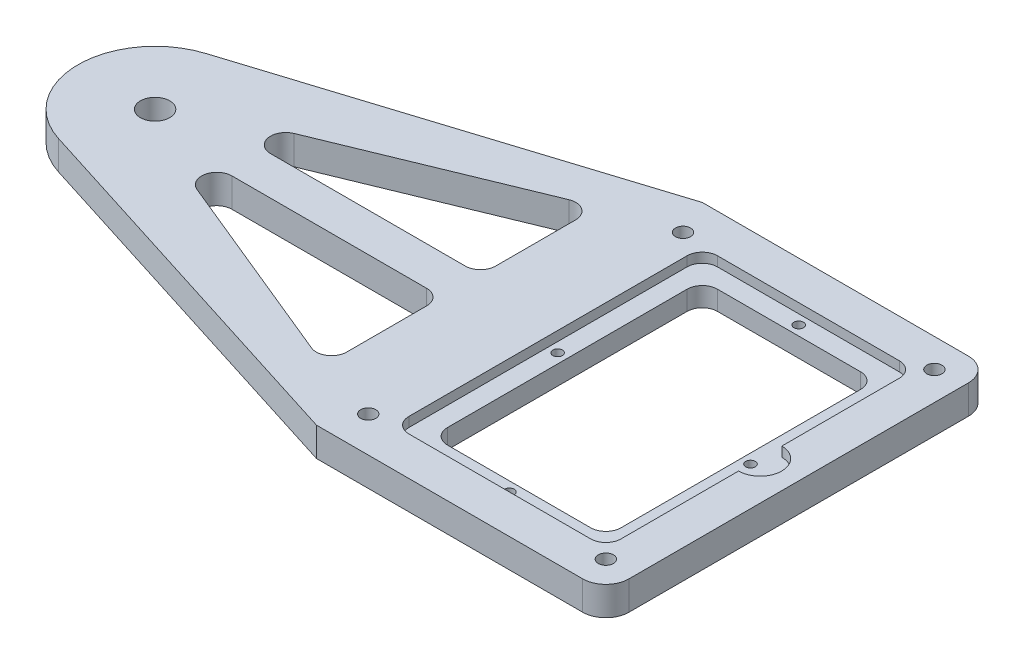
SolidWorks part; units mm, degrees
material "UHMW"
ref_plane "Front Plane" through (0, 0, 0) normal (0, 0, 1) x (1, 0, 0)
ref_plane "Top Plane" through (0, 0, 0) normal (0, 1, 0) x (1, 0, 0)
ref_plane "Right Plane" through (0, 0, 0) normal (1, 0, 0) x (0, 0, -1)
sketch "Sketch1" plane through (0, 0, 0) normal (0, 1, 0) x (1, 0, 0)
  line L0 (-47.625, 0) -> (47.625, 0) construction
  line L1 (-47.625, -63.5) -> (47.625, -63.5)
  line L2 (-47.625, -63.5) -> (-47.625, 63.5)
  line L3 (-47.625, 63.5) -> (47.625, 63.5)
  line L4 (47.625, -63.5) -> (47.625, 63.5)
  line L5 (-47.625, -63.5) -> (47.625, 63.5) construction
  line L6 (-47.625, 63.5) -> (47.625, -63.5) construction
  point P0 (0, 0)
  dimension "D1" = 95.25
  dimension "D2" = 127
  dimension "D3" = 63.5
extrude "Boss-Extrude1" add sketch "Sketch1" along normal blind 9.525
sketch "Sketch4" plane through (0, 9.525, 0) normal (0, 1, 0) x (1, 0, 0)
  line L1 (-47.625, 63.5) -> (-171.916, 24.2193)
  line L5 (-47.625, 63.5) -> (-47.625, -63.5) construction
  line L9 (-47.625, -63.5) -> (-171.916, -24.2193)
  line L10 (-47.625, 63.5) -> (-47.625, -63.5)
  arc A0 (-171.916, 24.2193) -> (-171.916, -24.2193) centre (-164.2618, 0) ccw
  circle A1 centre (-48.9458, 0) radius 2.5 construction
  dimension "D1" = 50.8
  dimension "D2" = 115.316
extrude "Boss-Extrude3" add sketch "Sketch4" against normal blind 9.525
sketch "Sketch5" plane through (0, 9.525, 0) normal (0, 1, 0) x (1, 0, 0)
  circle A0 centre (-164.2618, 0) radius 4.826
  circle A1 centre (-8.6868, 0) radius 4.826
  arc A2 (-171.916, 24.2193) -> (-171.916, -24.2193) centre (-164.2618, 0) ccw construction
  arc A3 (-171.916, 24.2193) -> (-171.916, -24.2193) centre (-164.2618, 0) ccw
  dimension "D1" = 9.652
  dimension "D2" = 155.575
extrude "Cut-Extrude1" cut sketch "Sketch5" against normal through all contours A0 | A1 region at (-164.2618, 9.525, 0) region at (-8.6868, 9.525, 0)
sketch "Sketch6" plane through (0, 9.525, 0) normal (0, 1, 0) x (1, 0, 0)
  line L0 (-63.5, 6.35) -> (-63.5, -6.35) construction
  line L1 (-63.5, 45.1637) -> (-157.9118, 6.35)
  line L2 (-157.9118, 6.35) -> (-63.5, 6.35)
  line L3 (-63.5, 6.35) -> (-63.5, 45.1637)
  line L4 (-63.5, -6.35) -> (-63.5, -45.1637)
  line L5 (-63.5, -45.1637) -> (-157.9118, -6.35)
  line L6 (-157.9118, -6.35) -> (-63.5, -6.35)
  line L7 (0, 0) -> (-63.5, 0) construction
  line L8 (-47.625, 63.5) -> (-171.916, 24.2193) construction
  line L9 (-189.6618, 78.2466) -> (-189.6618, -78.2466) construction
  arc A1 (-171.916, 24.2193) -> (-171.916, -24.2193) centre (-164.2618, 0) ccw construction
  point P10 (-189.6618, 0)
  dimension "D1" = 12.7
  dimension "D2" = 31.75
  dimension "D3" = 12.7
  dimension "D4" = 63.5
extrude "Cut-Extrude2" cut sketch "Sketch6" against normal through all
fillet "Fillet9" radius 5 6 edges at (-157.9118, 4.7625, 6.35) (-63.5, 4.7625, 6.35) (-63.5, 4.7625, 45.1637) (-63.5, 4.7625, -6.35) (-157.9118, 4.7625, -6.35) (-63.5, 4.7625, -45.1637)
sketch "Sketch7" plane through (0, 9.525, 0) normal (0, 1, 0) x (1, 0, 0)
  circle A0 centre (-8.6868, 0) radius 5.4538
extrude "Boss-Extrude4" add sketch "Sketch7" against normal blind 6.35
sketch "Sketch8" plane through (0, 9.525, 0) normal (0, 1, 0) x (1, 0, 0)
  line L4 (-47.625, -63.5) -> (47.625, -63.5) construction
  line L5 (-34.925, 50.8) -> (-34.925, -50.8)
  line L7 (-47.625, 63.5) -> (-47.625, -63.5) construction
  line L8 (-171.916, -24.2193) -> (-47.625, -63.5) construction
  line L10 (47.625, 50.8) -> (-47.625, 50.8)
  line L11 (34.925, 50.8) -> (-34.925, 50.8)
  line L13 (34.925, -63.5) -> (34.925, 63.5)
  line L14 (34.925, -50.8) -> (34.925, 50.8)
  line L15 (-34.925, 63.5) -> (-34.925, -63.5) construction
  line L16 (-47.625, -50.8) -> (47.625, -50.8)
  line L17 (-34.925, -50.8) -> (34.925, -50.8)
  dimension "D1" = 12.7
  dimension "D2" = 12.7
  dimension "D3" = 12.7
  dimension "D4" = 12.7
extrude "Cut-Extrude3" cut sketch "Sketch8" against normal blind 3.175
sketch "Sketch9" plane through (0, 6.35, 0) normal (0, 1, 0) x (1, 0, 0)
  line L14 (-28.575, -44.45) -> (28.575, -44.45)
  line L15 (28.575, -44.45) -> (28.575, 44.45)
  line L16 (-28.575, 44.45) -> (-28.575, -44.45)
  line L17 (28.575, 44.45) -> (-28.575, 44.45)
  line L18 (-28.575, -44.45) -> (28.575, -44.45)
  line L19 (28.575, -44.45) -> (28.575, 44.45)
  line L20 (-28.575, 44.45) -> (-28.575, -44.45)
  line L21 (28.575, 44.45) -> (-28.575, 44.45)
  dimension "D1" = 6.35
extrude "Cut-Extrude4" cut sketch "Sketch9" against normal through all
sketch "Sketch11" plane through (0, 6.35, 0) normal (0, 1, 0) x (1, 0, 0)
  line L0 (0, 50.8) -> (0, -50.8) construction
  line L1 (34.925, 50.8) -> (-34.925, 50.8) construction
  line L2 (-34.925, -50.8) -> (34.925, -50.8) construction
  line L3 (-34.925, 0) -> (34.925, 0) construction
  line L4 (-34.925, 50.8) -> (-34.925, -50.8) construction
  line L5 (34.925, -50.8) -> (34.925, 50.8) construction
  line L6 (-34.925, 50.8) -> (-34.925, -50.8) construction
  line L7 (-28.575, 44.45) -> (-28.575, -44.45) construction
  line L8 (34.925, 50.8) -> (-34.925, 50.8) construction
  circle A0 centre (-31.75, 0) radius 1.5875
  circle A1 centre (31.75, 0) radius 1.5875
  circle A2 centre (0, 47.625) radius 1.5875
  circle A3 centre (0, -47.625) radius 1.5875
  dimension "D1" = 3.175
  dimension "D4" = 3.175
  dimension "D2" = 3.175
  dimension "D3" = 3.175
  dimension "D5" = 3.175
extrude "Cut-Extrude6" cut sketch "Sketch11" against normal through all
sketch "Sketch12" plane through (0, 9.525, 0) normal (0, 1, 0) x (1, 0, 0)
  line L0 (34.925, -50.8) -> (34.925, 50.8) construction
  line L1 (34.925, 7.112) -> (34.925, 50.8) construction
  line L2 (34.925, -7.112) -> (34.925, -50.8) construction
  line L3 (34.925, 0) -> (-34.925, 0) construction
  line L4 (-34.925, 50.8) -> (-34.925, -50.8) construction
  line L5 (34.925, -50.8) -> (34.925, 50.8) construction
  line L6 (34.925, 7.112) -> (34.925, -7.112)
  arc A0 (34.925, 7.112) -> (34.925, -7.112) centre (34.925, 0) cw
  dimension "D1" = 7.112
extrude "Cut-Extrude7" cut sketch "Sketch12" against normal blind 3.175
fillet "Fillet10" radius 5 4 edges at (-34.925, 7.9375, 50.8) (34.925, 7.9375, 50.8) (34.925, 7.9375, -50.8) (-34.925, 7.9375, -50.8)
fillet "Fillet11" radius 5 4 edges at (-28.575, 3.175, -44.45) (28.575, 3.175, -44.45) (28.575, 3.175, 44.45) (-28.575, 3.175, 44.45)
fillet "Fillet12" radius 7.62 2 edges at (47.625, 4.7625, -63.5) (47.625, 4.7625, 63.5)
sketch "Sketch13" plane through (0, 9.525, 0) normal (0, 1, 0) x (1, 0, 0)
  circle A0 centre (-42.2861, 51.8111) radius 2.4892
  circle A1 centre (-42.2861, -51.8111) radius 2.4892
  circle A2 centre (38.2023, -54.0773) radius 2.4892
  circle A3 centre (38.2023, 54.0773) radius 2.4892
  dimension "D1" = 4.9784
extrude "Cut-Extrude8" cut sketch "Sketch13" against normal through all
